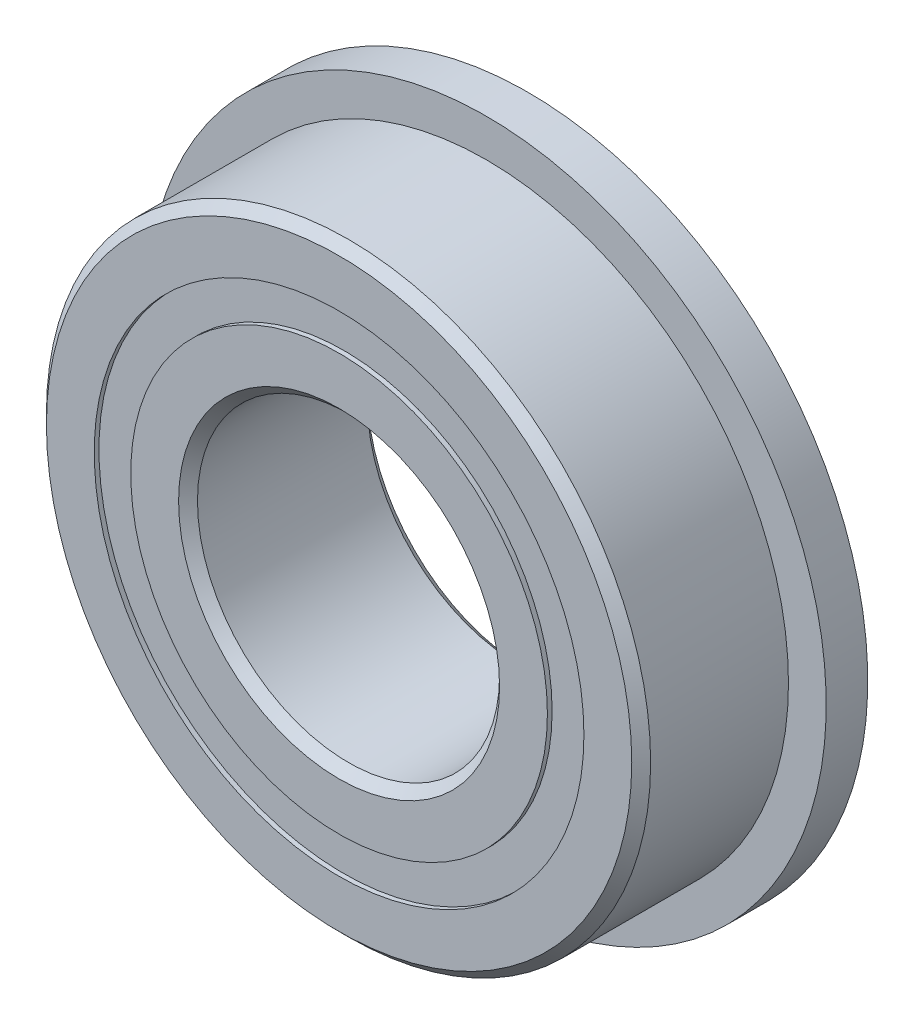
SolidWorks part; units mm, degrees
material "AISI 1020"
ref_plane "Front Plane" through (0, 0, 0) normal (0, 0, 1) x (1, 0, 0)
ref_plane "Top Plane" through (0, 0, 0) normal (0, 1, 0) x (1, 0, 0)
ref_plane "Right Plane" through (0, 0, 0) normal (1, 0, 0) x (0, 0, -1)
sketch "Sketch1" plane through (0, 0, 0) normal (1, 0, 0) x (0, 0, -1)
  line L0 (-2.5, 0) -> (2.5, 0) construction
  line L1 (0, 8) -> (0, -8) construction
  line L2 (2.25, 8) -> (-2.25, 8)
  line L3 (-2.25, 8) -> (-2.5, 7.75)
  line L4 (-2.5, 7.75) -> (-2.5, 6.4835)
  line L5 (-2.5, 6.4835) -> (-1.1111, 6.4835)
  line L6 (2.5, 6.4835) -> (1.1111, 6.4835)
  line L7 (2.5, 7.75) -> (2.5, 6.4835)
  line L8 (2.25, 8) -> (2.5, 7.75)
  line L9 (0, 8) -> (0, 6) construction
  line L10 (0, 6) -> (0, 4) construction
  arc A0 (-1.1111, 6.4835) -> (1.1111, 6.4835) centre (0, 6) cw
  point P14 (0, 4)
  dimension "Width" = 5
  dimension "OD" = 16
  dimension "D1" = 45
  dimension "D2" = 0.25
  dimension "Shaft Dia" = 8
  dimension "D3" = 2.2222
  dimension "D4" = 0.4835
revolve "Revolve1" add sketch "Sketch1" angle 360 about L0
sketch "Sketch3" plane through (0, 0, 0) normal (1, 0, 0) x (0, 0, -1)
  line L0 (-2.5, 5.5165) -> (-1.1111, 5.5165)
  line L1 (0, 8) -> (0, -8) construction
  line L2 (-2.5, 7.75) -> (-2.5, 6.4835) construction
  line L3 (-2.5, 5.5165) -> (-2.5, 4.25)
  line L4 (-2.25, 8) -> (-2.5, 7.75) construction
  line L5 (-2.5, 4.25) -> (-2.25, 4)
  line L6 (-2.25, 4) -> (2.25, 4)
  line L7 (2.25, 8) -> (2.25, -8) construction
  line L8 (2.25, 4) -> (2.5, 4.25)
  line L9 (2.5, -7.75) -> (2.5, 7.75) construction
  line L10 (2.5, 4.25) -> (2.5, 5.5165)
  line L11 (2.5, 5.5165) -> (1.1111, 5.5165)
  line L13 (2.25, 8) -> (2.5, 7.75) construction
  arc A0 (1.1111, 6.4835) -> (-1.1111, 6.4835) centre (0, 6) ccw construction
  arc A1 (1.1111, 5.5165) -> (-1.1111, 5.5165) centre (0, 6) cw
revolve "Revolve3" add sketch "Sketch3" angle 360 about L0
sketch "Sketch4" plane through (0, 0, 0) normal (1, 0, 0) x (0, 0, -1)
  line L0 (-1.2118, 6) -> (1.2118, 6)
  arc A2 (-1.2118, 6) -> (1.2118, 6) centre (0, 6) cw
  arc A3 (1.1111, 6.4835) -> (-1.1111, 6.4835) centre (0, 6) ccw construction
revolve "Revolve4" add sketch "Sketch4" angle 360 about L0
ref_axis "Axis1" through (0, 0, -2.5) along (0, 0, 1)
pattern_circular "CirPattern1" count 12 every 30 about axis through (0, 0, -2.5) along (0, 0, 1) of bodies 104
sketch "Sketch5" plane through (0, 0, 0) normal (1, 0, 0) x (0, 0, -1)
  line L0 (-2.5, 6.4835) -> (-1.1111, 6.4835) construction
  line L1 (-2.375, 6.4835) -> (-1.2118, 6.4835)
  line L2 (-2.375, 6.4835) -> (-2.375, 5.5165)
  line L3 (-2.375, 5.5165) -> (-1.2118, 5.5165)
  line L4 (-1.2118, 6.4835) -> (-1.2118, 5.5165)
  line L5 (-2.5, 5.5165) -> (-1.1111, 5.5165) construction
  line L6 (2.5, 6.4835) -> (1.1111, 6.4835) construction
  line L7 (2.375, 6.4835) -> (1.2118, 6.4835)
  line L8 (2.375, 6.4835) -> (2.375, 5.5165)
  line L9 (2.375, 5.5165) -> (1.2118, 5.5165)
  line L10 (1.2118, 6.4835) -> (1.2118, 5.5165)
  line L11 (2.5, 5.5165) -> (1.1111, 5.5165) construction
  line L12 (-2.25, 8) -> (-2.5, 7.75) construction
  point P18 (-2.375, 7.875)
revolve "Revolve5" add sketch "Sketch5" angle 360 about L0
sketch "Sketch6" plane through (0, 0, 0) normal (1, 0, 0) x (0, 0, -1)
  line L0 (2.5, 0) -> (-2.5, 0) construction
  line L1 (2.5, 6.4835) -> (1.4, 6.4835)
  line L2 (2.5, 6.4835) -> (2.5, 9)
  line L3 (2.5, 9) -> (1.4, 9)
  line L4 (1.4, 6.4835) -> (1.4, 9)
  dimension "Th" = 1.1
  dimension "Flange OD" = 18
revolve "Revolve6" add sketch "Sketch6" angle 360 about L0
move or copy body "Body-Move/Copy1" [suppressed] bodies to move or copy 103 104 122 123 124 125 126 127 128 129 130 131 132 137 138 139
equation "\"D2@Sketch1\" = \"Width@Sketch1\"*.05"
equation "\"D3@Sketch1\" = \"Width@Sketch1\"/2.25"
equation "\"D4@Sketch1\" = (((\"OD@Sketch1\"-\"Width@Sketch1\")/2)/3.25)/3.5"
equation "\"D2@CirPattern1\" = 360/\"Balls@CirPattern1\""
